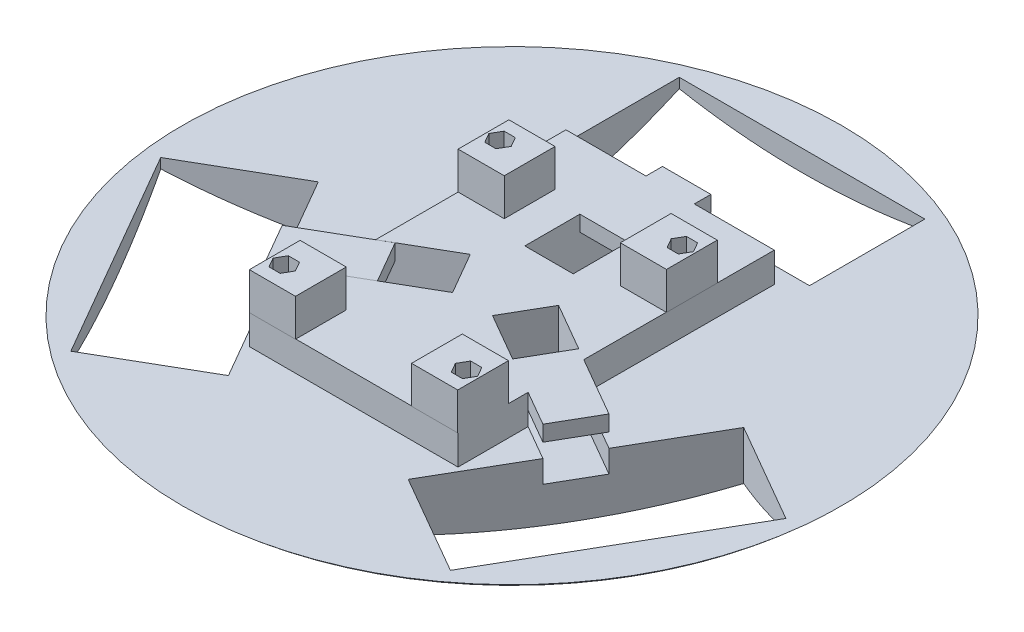
SolidWorks part; units mm, degrees
ref_plane "Front Plane" through (0, 0, 0) normal (0, 0, 1) x (1, 0, 0)
ref_plane "Top Plane" through (0, 0, 0) normal (0, 1, 0) x (1, 0, 0)
ref_plane "Right Plane" through (0, 0, 0) normal (1, 0, 0) x (0, 0, -1)
sketch "Sketch2" plane through (0, 0, 0) normal (0, 1, 0) x (1, 0, 0)
  line L0 (0, -68.0098) -> (0, 65.7503) construction
  line L1 (-33, 77.9495) -> (33, 77.9495)
  line L2 (-33, 77.9495) -> (-33, 46.9495)
  line L3 (-33, 46.9495) -> (33, 46.9495)
  line L4 (33, 77.9495) -> (33, 46.9495)
  line L5 (-33, 77.9495) -> (33, 46.9495) construction
  line L6 (-33, 46.9495) -> (33, 77.9495) construction
  line L7 (-70.2148, 0) -> (95.7201, 0) construction
  line L8 (0, 0) -> (-72.5813, -41.9048) construction
  line L9 (0, 0) -> (72.5813, -41.9048) construction
  line L10 (84.0062, -10.3959) -> (51.0062, -67.5536)
  line L11 (57.1594, 5.1041) -> (24.1594, -52.0536)
  line L12 (84.0062, -10.3959) -> (57.1594, 5.1041)
  line L13 (51.0062, -67.5536) -> (24.1594, -52.0536)
  line L14 (-51.0062, -67.5536) -> (-84.0062, -10.3959)
  line L15 (-24.1594, -52.0536) -> (-57.1594, 5.1041)
  line L16 (-51.0062, -67.5536) -> (-24.1594, -52.0536)
  line L17 (-84.0062, -10.3959) -> (-57.1594, 5.1041)
  line L18 (-6.5, -8.0505) -> (6.5, 46.9495) construction
  line L19 (-6.5, 46.9495) -> (6.5, 46.9495)
  line L20 (-6.5, 46.9495) -> (-6.5, -8.0505)
  line L21 (-6.5, -8.0505) -> (6.5, -8.0505)
  line L22 (6.5, 46.9495) -> (6.5, -8.0505)
  line L23 (-6.5, 46.9495) -> (6.5, -8.0505) construction
  line L24 (31.4023, -15.1408) -> (6.5, -0.7634)
  line L25 (-6.1216, -8.0505) -> (0, 2.5524)
  line L26 (24.9023, -26.3991) -> (0, -12.0218)
  line L27 (-25.0514, -26.4852) -> (0, -12.0218)
  line L28 (0, 2.5524) -> (6.1216, -8.0505)
  line L29 (-33.4324, -16.3129) -> (-6.5, -0.7634)
  circle A2 centre (0, 0) radius 16 construction
  point P3 (0, 19.4495)
  point P4 (0, 46.9495)
  point P6 (0, 62.4495)
  point P13 (0, 0)
  point P33 (0, 0)
  point P41 (0, -4.5162)
  dimension "D1" = 55
  dimension "D2" = 13
  dimension "D3" = 32
  dimension "D5" = 66
  dimension "D6" = 120
  dimension "D7" = 31
  dimension "D8" = 3
  dimension "D4" = 3
sketch "Sketch3" plane through (0, 0, 0) normal (1, 0, 0) x (0, 0, -1)
  line L0 (0, 83.7838) -> (0, -101.0811) construction
  line L1 (-115.9459, 0) -> (127.2973, 0) construction
  line L5 (0, 20) -> (0, 0)
  line L6 (88.569, 20) -> (0, 20)
  arc A3 (84.754, 17.3868) -> (0, 0) centre (7.3808, 179.2865) cw
  arc A4 (84.754, 17.3868) -> (88.569, 20) centre (78.286, 30.9207) ccw
  point P13 (90, 5.0684)
  dimension "D5" = 179.4384
  dimension "D1" = 15
  dimension "D2" = 20
  dimension "D3" = 20
  dimension "D4" = 90
revolve "Revolve1" add sketch "Sketch3" angle 360 about L5
extrude "Cut-Extrude1" cut sketch "Sketch2" along normal blind 40 contours L3 L4 L1 L2 | L15 L17 L14 L16 | L11 L13 L10 L12
sketch "Sketch4" plane through (0, 20, 0) normal (0, 1, 0) x (1, 0, 0)
  line L1 (-6.5, 46.9495) -> (6.5, 46.9495)
  line L2 (-6.5, 46.9495) -> (-6.5, 9.9495)
  line L3 (-6.5, 9.9495) -> (6.5, 9.9495)
  line L4 (6.5, 46.9495) -> (6.5, 9.9495)
  line L5 (-6.5, 46.9495) -> (6.5, 9.9495) construction
  line L6 (-6.5, 9.9495) -> (6.5, 46.9495) construction
  line L7 (43.9094, -17.8456) -> (37.4094, -29.1039)
  line L8 (-57.1594, 5.1041) -> (-24.1594, -52.0536) construction
  line L9 (-33, 46.9495) -> (33, 46.9495) construction
  line L10 (57.1594, 5.1041) -> (24.1594, -52.0536) construction
  line L26 (43.9094, -17.8456) -> (11.8665, 0.6544)
  line L27 (37.4094, -29.1039) -> (5.3665, -10.6039)
  line L28 (11.8665, 0.6544) -> (5.3665, -10.6039)
  line L29 (-37.4094, -29.1039) -> (-43.9094, -17.8456)
  line L30 (-37.4094, -29.1039) -> (-5.3665, -10.6039)
  line L31 (-43.9094, -17.8456) -> (-11.8665, 0.6544)
  line L32 (-5.3665, -10.6039) -> (-11.8665, 0.6544)
  line L33 (51.0062, -67.5536) -> (40.4434, -61.4551)
  line L34 (51.0062, -67.5536) -> (24.1594, -52.0536) construction
  line L35 (51.0062, -67.5536) -> (84.0062, -10.3959)
  line L36 (84.0062, -10.3959) -> (73.4434, -4.2974)
  line L37 (84.0062, -10.3959) -> (57.1594, 5.1041) construction
  circle A0 centre (0, 0) radius 88.569 construction
  circle A1 centre (0, 0) radius 73.569 construction
  arc A2 (40.4434, -61.4551) -> (73.4434, -4.2974) centre (0, 0) ccw
  circle A3 centre (0, 0) radius 84.647
  point P0 (0, 28.4495)
  point P5 (0, 46.9495)
  point P22 (0, 0)
  point P23 (0, 4.0327)
  point P32 (-2.3282, 4.0326)
  line M8 (-57.1594, 5.1041) -> (-24.1594, -52.0536)
  line M13 (24.1594, -52.0536) -> (57.1594, 5.1041)
  line M17 (33, 46.9495) -> (-33, 46.9495)
  dimension "D4" = 177.1379
  dimension "D5" = 147.1379
  dimension "D6" = 169.2941
  dimension "D1" = 13
  dimension "D2" = 37
  dimension "D3" = 15
extrude "Cut-Extrude2" cut sketch "Sketch4" against normal blind 6 contours L4 L2 L3 M17 | L30 L32 L31 M8 | L26 L28 L27 M13 region at (0, 20, -28.4495) region at (24.638, 20, 14.2247) region at (-24.638, 20, 14.2247)
sketch "Sketch5" plane through (0, 20, 0) normal (0, 1, 0) x (1, 0, 0)
  line L1 (-28, 42.5) -> (-6.5, 42.5)
  line L2 (-28, 42.5) -> (-28, -8.6603)
  line L3 (-28, -42.5) -> (28, -42.5)
  line L5 (-28, 42.5) -> (28, -42.5) construction
  line L6 (-28, -42.5) -> (28, 42.5) construction
  line L7 (-37.4094, -29.1039) -> (-5.3665, -10.6039) construction
  line L10 (-43.9094, -17.8456) -> (-11.8665, 0.6544) construction
  line L12 (37.4094, -29.1039) -> (5.3665, -10.6039) construction
  line L18 (6.5, 46.9495) -> (6.5, 9.9495) construction
  line L19 (6.5, 46.9495) -> (6.5, 9.9495) construction
  line L20 (-28, -23.6714) -> (-28, -42.5)
  line L21 (28, -23.6714) -> (28, -42.5)
  line L22 (6.5, 42.5) -> (28, 42.5)
  line L23 (0, 13.9495) -> (0, -42.8187) construction
  line L24 (28, 42.5) -> (27.888, -8.5956)
  line L26 (-6.5, 46.9495) -> (-6.5, 9.9495) construction
  line L27 (43.9094, -17.8456) -> (11.8665, 0.6544) construction
  line L28 (27.888, -8.5956) -> (11.8665, 0.6544)
  line L29 (11.8665, 0.6544) -> (5.3665, -10.6039)
  line L30 (-28, -8.6603) -> (-11.8665, 0.6544)
  line L31 (-11.8665, 0.6544) -> (-5.3665, -10.6039)
  line L32 (-6.5, 42.5) -> (-6.5, 9.9495)
  line L33 (-6.5, 9.9495) -> (6.5, 9.9495)
  line L34 (-5.3665, -10.6039) -> (-28, -23.6714)
  line L35 (5.3665, -10.6039) -> (28, -23.6714)
  line L36 (6.5, 9.9495) -> (6.5, 42.5)
  line L40 (0, -51.0669) -> (0, 44.2573) construction
  line L41 (-47.7731, 0) -> (43.2855, 0) construction
  point P0 (0, 0)
  dimension "D1" = 56
  dimension "D2" = 85
extrude "Boss-Extrude1" add sketch "Sketch5" along normal blind 8
sketch "Sketch6" plane through (0, 28, 0) normal (0, 1, 0) x (1, 0, 0)
  line L0 (-15.5977, 13.519) -> (-15.5977, 27.1605)
  line L1 (-15.5977, 27.1605) -> (-28, 27.1605)
  line L2 (-28, 27.1605) -> (-28, 13.519)
  line L3 (-28, 13.519) -> (-15.5977, 13.519)
  line L4 (-28, 42.5) -> (-28, -8.6603) construction
  line L5 (21.4978, 21.2855) -> (22.9989, 23.8855)
  line L6 (0, -54.2519) -> (0, 64.1127) construction
  line L7 (-46.6508, -7.7145) -> (37.9333, -7.7145) construction
  line L8 (28, 13.519) -> (15.5977, 13.519)
  line L9 (15.5977, 13.519) -> (15.5977, 27.1605)
  line L10 (15.5977, 27.1605) -> (28, 27.1605)
  line L11 (28, 27.1605) -> (28, 13.519)
  line L12 (15.5977, -28.948) -> (15.5977, -42.5894)
  line L13 (28, -28.948) -> (15.5977, -28.948)
  line L14 (28, -42.5894) -> (28, -28.948)
  line L15 (15.5977, -42.5894) -> (28, -42.5894)
  line L16 (-28, -42.5894) -> (-28, -28.948)
  line L17 (-28, -28.948) -> (-15.5977, -28.948)
  line L18 (-15.5977, -28.948) -> (-15.5977, -42.5894)
  line L19 (-15.5977, -42.5894) -> (-28, -42.5894)
  line L20 (-21.4978, 21.2855) -> (-22.9989, 23.8855)
  line L21 (-22.9989, 23.8855) -> (-26.0011, 23.8855)
  line L22 (-26.0011, 23.8855) -> (-27.5022, 21.2855)
  line L23 (-27.5022, 21.2855) -> (-26.0011, 18.6855)
  line L24 (-26.0011, 18.6855) -> (-22.9989, 18.6855)
  line L25 (-22.9989, 18.6855) -> (-21.4978, 21.2855)
  line L26 (22.9989, 18.6855) -> (21.4978, 21.2855)
  line L27 (26.0011, 18.6855) -> (22.9989, 18.6855)
  line L28 (27.5022, 21.2855) -> (26.0011, 18.6855)
  line L29 (26.0011, 23.8855) -> (27.5022, 21.2855)
  line L30 (22.9989, 23.8855) -> (26.0011, 23.8855)
  line L31 (-21.4978, -36.7145) -> (-22.9989, -39.3145)
  line L32 (-22.9989, -39.3145) -> (-26.0011, -39.3145)
  line L33 (-26.0011, -39.3145) -> (-27.5022, -36.7145)
  line L34 (-27.5022, -36.7145) -> (-26.0011, -34.1145)
  line L35 (-26.0011, -34.1145) -> (-22.9989, -34.1145)
  line L36 (-22.9989, -34.1145) -> (-21.4978, -36.7145)
  line L37 (26.0011, -39.3145) -> (27.5022, -36.7145)
  line L38 (22.9989, -39.3145) -> (26.0011, -39.3145)
  line L39 (21.4978, -36.7145) -> (22.9989, -39.3145)
  line L40 (22.9989, -34.1145) -> (21.4978, -36.7145)
  line L41 (26.0011, -34.1145) -> (22.9989, -34.1145)
  line L42 (27.5022, -36.7145) -> (26.0011, -34.1145)
  circle A0 centre (-24.5, 21.2855) radius 2.6 construction
  point P5 (0, 0)
  point P38 (26.7517, 22.5855)
  dimension "D3" = 5.2
  dimension "D1" = 29
  dimension "D2" = 24.5
  dimension "D4" = 15.5977
  dimension "D5" = 13.6415
extrude "Boss-Extrude2" add sketch "Sketch6" along normal blind 10
sketch "Sketch7" plane through (-3.25, 0, -5.6292) normal (0.5, 0, 0.866) x (0.866, 0, -0.5)
  line L0 (-46.9495, 14) -> (-46.9495, 33.5813) construction
  line L1 (-24.7351, 23.7906) -> (-46.9495, 23.7906)
  line L3 (-46.9495, 23.7906) -> (-46.9495, 27.9906)
  line L4 (-46.9495, 27.9906) -> (-24.7351, 27.9906)
  line L5 (-24.7351, 27.9906) -> (-24.7351, 23.7906)
  point P11 (0, 0)
  point P12 (0, 0)
  point P13 (-28.5788, 28)
  point P15 (0, 0)
  point P16 (0, 0)
  dimension "D1" = 4.2
  dimension "D2" = 0
  dimension "D3" = 22.2144
extrude "Boss-Extrude4" add sketch "Sketch7" along normal up to surface (13 mm away) separate body up to face at (-23.592, 20.6667, 21.1264)
sketch "Sketch8" plane through (3.25, 0, -5.6292) normal (-0.5, 0, 0.866) x (0.866, 0, 0.5)
  line L0 (46.9495, 20) -> (46.9495, 32.4167) construction
  line L1 (24.7395, 28) -> (46.9495, 28)
  line L2 (46.9495, 28) -> (46.9495, 23.8)
  line L3 (46.9495, 23.8) -> (24.7395, 23.8)
  line L5 (24.7395, 23.8) -> (24.7395, 28)
  point P6 (0, 0)
  point P9 (0, 0)
  point P13 (0, 0)
  dimension "D1" = 4.2
  dimension "D2" = 22.21
extrude "Boss-Extrude5" add sketch "Sketch8" along normal up to surface (13 mm away) up to face at (23.592, 20.6667, 21.1264)
sketch "Sketch9" plane through (-6.5, 0, 0) normal (1, 0, 0) x (0, 0, -1)
  line L0 (46.9495, 20) -> (46.9495, 31.8214) construction
  line L1 (42.5, 28) -> (46.9495, 28)
  line L2 (46.9495, 28) -> (46.9495, 23.8)
  line L3 (46.9495, 23.8) -> (24.7395, 23.8)
  line L4 (24.7395, 23.8) -> (24.7395, 28)
  line L5 (13.519, 28) -> (27.1605, 28) construction
  line L6 (24.7395, 28) -> (42.5, 28)
  dimension "D1" = 22.21
  dimension "D2" = 4.2
extrude "Boss-Extrude6" add sketch "Sketch9" along normal up to surface (13 mm away) up to face at (6.5, 20.6667, -33.133)
